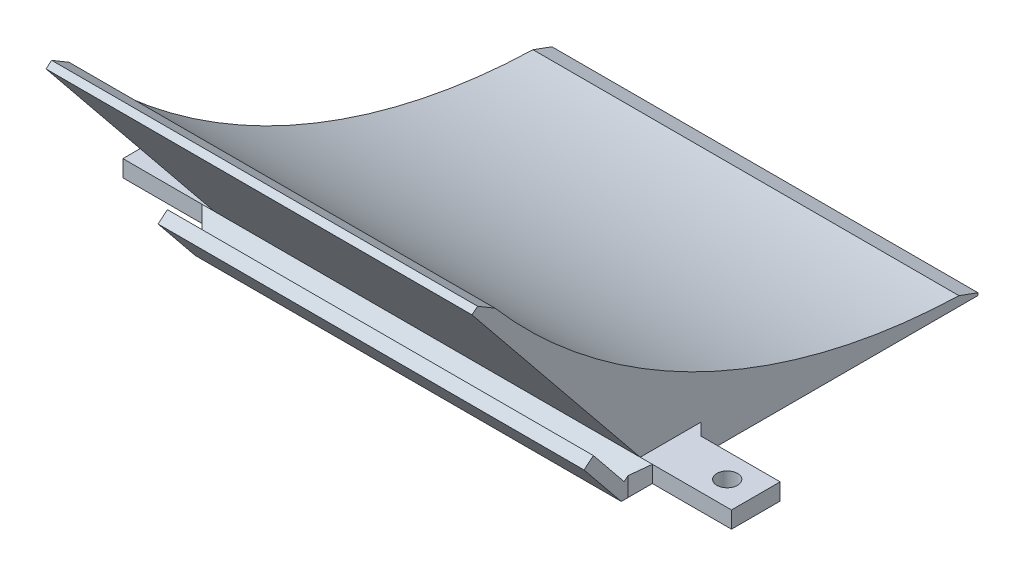
SolidWorks part; units mm, degrees
ref_plane "Front Plane" through (0, 0, 0) normal (0, 0, 1) x (1, 0, 0)
ref_plane "Top Plane" through (0, 0, 0) normal (0, 1, 0) x (1, 0, 0)
ref_plane "Right Plane" through (0, 0, 0) normal (1, 0, 0) x (0, 0, -1)
sketch "Sketch2" plane through (93.0034, 0, 0) normal (-1, 0, 0) x (0, 0, 1)
  line L0 (0, 0) -> (206.9217, 0) construction
  line L1 (210.0714, 3.884) -> (206.9217, 0) construction
  line L2 (207.7413, 5.7736) -> (203.0593, 0) construction
  line L3 (210.0714, 3.884) -> (229.5972, 27.9619) construction
  line L4 (207.7413, 5.7736) -> (227.2671, 29.8515) construction
  line L5 (207.46, 5.7442) -> (210.1008, 3.6027)
  line L6 (151.9511, 2.5) -> (204.8291, 2.5) construction
  line L7 (210.0714, 3.884) -> (207.7413, 5.7736) construction
  line L8 (208.9064, 4.8288) -> (208.7804, 4.6735) construction
  line L9 (210.1008, 3.6027) -> (215.1397, 9.8164)
  line L10 (207.46, 5.7442) -> (235.095, 39.822)
  line L11 (215.1397, 9.8164) -> (216.6931, 8.5566)
  line L12 (216.6931, 8.5566) -> (210.5651, 1)
  line L13 (210.5651, 1) -> (151.9511, 1)
  line L14 (235.095, 39.822) -> (233.3086, 41.2707)
  line L18 (151.9511, 1) -> (151.9511, 2.5)
  line L19 (210.0714, 3.884) -> (229.5972, 27.9619) construction
  line L20 (207.7413, 5.7736) -> (227.2671, 29.8515) construction
  line L21 (210.0714, 3.884) -> (207.7413, 5.7736) construction
  line L26 (186.7375, 34.25) -> (184.1069, 39.7702) construction
  line L27 (203.0593, 0) -> (186.7375, 34.25) construction
  arc A0 (233.3086, 41.2707) -> (151.9511, 2.5) centre (151.9511, 107.2468) cw
  point P11 (208.7804, 4.6735)
  point P27 (197.0128, 12.6881)
  dimension "D6" = 1.5
  dimension "D7" = 8
  dimension "D1" = 0.2
  dimension "D2" = 0.2
  dimension "D3" = 2
  dimension "D4" = 1
  dimension "D5" = 30
  dimension "D11" = 6.115
extrude "Boss-Extrude1" add sketch "Sketch2" against normal up to surface (70 mm away) contours L14 A0 L18 L13 L12 L11 L9 L5 L10 region at (93.0034, 11.0697, 200.16)
chamfer "Chamfer1" distance 1.1 distance2 3 1 edges at (128.0034, 2.5, 151.9511) first distance on face at (128.0034, 1.75, 151.9511)
chamfer "Chamfer2" distance 3 distance2 1.1 1 edges at (128.0034, 41.2707, 233.3086) first distance on face at (128.0034, 17.6401, 196.3065)
sketch "Sketch3" plane through (93.0034, 0, 0) normal (-1, 0, 0) x (0, 0, 1)
  line L0 (210.5651, 1) -> (151.9511, 1) construction
  line L1 (207.46, 5.7442) -> (199.46, 5.7442)
  line L2 (207.46, 5.7442) -> (207.46, 3)
  line L3 (207.46, 3) -> (199.46, 3)
  line L4 (199.46, 5.7442) -> (199.46, 3)
  dimension "D1" = 2
  dimension "D2" = 8
extrude "Boss-Extrude2" add sketch "Sketch3" along normal blind 15
hole_wizard "M3 Clearance Hole1" positions "Sketch6" profile "Sketch5" hole size "M3" standard "ANSI Metric" end condition through all
sketch "Sketch6" plane through (0, 5.7442, 0) normal (0, 1, 0) x (1, 0, 0)
  line L0 (78.0034, -203.46) -> (82.7034, -203.46) construction
  line L1 (78.0034, -207.46) -> (78.0034, -199.46) construction
  point P2 (82.7034, -203.46)
  point P10 (82.7034, -203.46)
  dimension "D1" = 4.7
sketch "Sketch5" plane through (82.7034, 5.7442, 203.46) normal (1, 0, 0) x (0, 0, 1)
  line L0 (0, 0) -> (0, 4.7442)
  line L1 (0, 4.7442) -> (1.7, 4.7442)
  line L2 (1.7, 4.7442) -> (1.7, 0)
  line L5 (1.7, 0) -> (0, 0)
  line L11 (0, -6.35) -> (0, 107.95) construction
  dimension "Thru Hole Dia." = 3.4
  dimension "Thru Hole Depth" = 4.7442
ref_plane "Bisection" through (128.0034, 0, 0) normal (1, 0, 0) x (0, 0, -1)
mirror "Mirror1" about plane through (128.0034, 0, 0) normal (1, 0, 0) of "Boss-Extrude2", "M3 Clearance Hole1"
chamfer "Chamfer3" distance 2 angle 45 6 edges at (163.0034, 4.3721, 207.46) (163.0034, 4.3721, 199.46) (163.0034, 3, 203.46) (93.0034, 4.3721, 199.46) (93.0034, 4.3721, 207.46) (93.0034, 3, 203.46)
